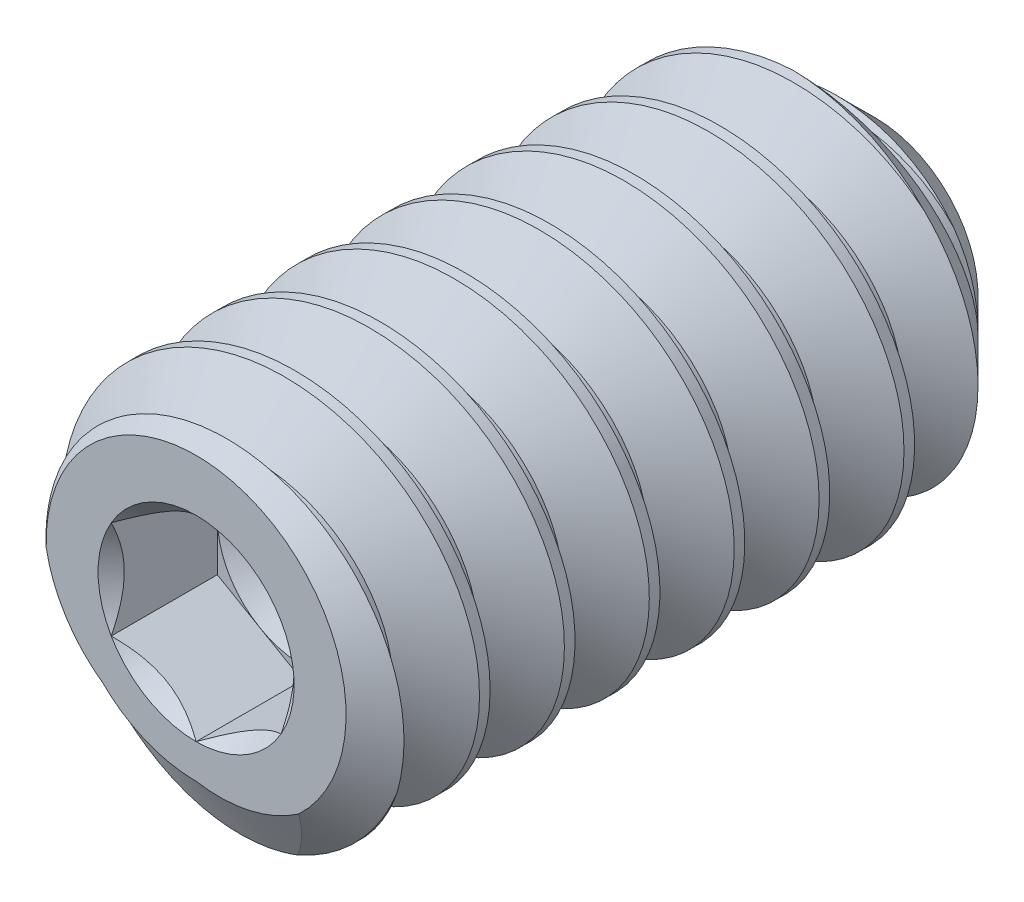
SolidWorks part; units mm, degrees
ref_plane "Front" through (0, 0, 0) normal (0, 0, 1) x (1, 0, 0)
ref_plane "Top" through (0, 0, 0) normal (0, 1, 0) x (1, 0, 0)
ref_plane "Right" through (0, 0, 0) normal (1, 0, 0) x (0, 0, -1)
sketch "Sketch22" plane through (0, 0, 0) normal (1, 0, 0) x (0, 0, -1)
  line L0 (-2.8865, 0) -> (-2.8865, 1.4021)
  line L1 (-2.8865, 1.4021) -> (-2.641, 1.7526)
  line L2 (-2.641, 1.7526) -> (2.6713, 1.7526)
  line L3 (2.6713, 1.7526) -> (3.4635, 0.9604)
  line L4 (3.4635, 0.9604) -> (2.8865, 0)
  line L5 (2.8865, 0) -> (-2.8865, 0)
  line L6 (2.8865, 0) -> (3.4635, 0) construction
  line L7 (3.4635, 0) -> (3.4635, 0.9604) construction
  line L8 (3.4635, -0.9604) -> (2.8865, 0) construction
  line L9 (-2.641, -1.7526) -> (2.6713, -1.7526) construction
  dimension "Dia" = 3.5052
  dimension "Length" = 6.35
  dimension "D3" = 35
  dimension "D5" = 118
  dimension "D6" = 45
  dimension "D7" = 2.8042
revolve "Revolve1" add sketch "Sketch22" angle 360 about L6
ref_plane "Plane1" through (0, 0, -3.4635) normal (0, 0, 1) x (1, 0, 0)
sketch "Sketch27" plane through (0, 0, -3.4635) normal (0, 0, 1) x (1, 0, 0)
  circle A0 centre (0, 0) radius 1.7526 construction
  circle A1 centre (0, 0) radius 1.7526
sketch "Sketch23" plane through (0, 0, 2.8865) normal (0, 0, 1) x (1, 0, 0)
  line L1 (0, 0.9165) -> (-0.7937, 0.4583)
  line L2 (-0.7937, 0.4583) -> (-0.7938, -0.4583)
  line L3 (-0.7938, -0.4583) -> (0, -0.9165)
  line L4 (0, -0.9165) -> (0.7937, -0.4583)
  line L5 (0.7937, -0.4583) -> (0.7937, 0.4583)
  line L6 (0.7937, 0.4583) -> (0, 0.9165)
  circle A0 centre (0, 0) radius 0.7938 construction
  dimension "Hex" = 1.5875
extrude "Cut-Extrude10" cut sketch "Sketch23" against normal blind 0.9922
sketch "Sketch24" plane through (0, 0, 2.8865) normal (0, 0, 1) x (1, 0, 0)
  circle A0 centre (0, 0) radius 0.9165
extrude "Cut-Extrude11" cut sketch "Sketch24" against normal through all draft 45
sketch "Sketch26" plane through (0, 0, 1.8943) normal (0, 0, 1) x (1, 0, 0)
  circle A0 centre (0, 0) radius 0.7938 construction
  circle A1 centre (0, 0) radius 0.7938
extrude "Cut-Extrude12" cut sketch "Sketch26" against normal through all draft 60
sketch "Sketch30" plane through (0, 0, 0) normal (1, 0, 0) x (0, 0, -1)
  line L0 (-2.641, 1.7526) -> (2.6713, 1.7526) construction
  line L1 (-2.8865, 0) -> (-2.8865, 1.4021) construction
  line L2 (3.4635, 0) -> (3.4635, 0.9604) construction
  line L3 (-2.641, -1.7526) -> (2.6713, -1.7526) construction
  point P0 (-2.8865, 1.7526)
  point P1 (3.4635, 1.7526)
  point P2 (3.4635, -1.7526)
  point P11 (0.6854, -1.7526)
  dimension "D1" = 2.7781
sketch "Sketch31" plane through (0, 0, 0) normal (1, 0, 0) x (0, 0, -1)
  line L2 (2.8865, 0) -> (3.4635, -0.9604)
  line L3 (3.4635, 0.9604) -> (2.8865, 0)
ref_axis "Center Axis 1" through (0, 0, -10.7974) along (0, 0, 1)
ref_plane "Contact Plane 1" through (0, 0, 2.8865) normal (0, 0, -1) x (0, 1, 0)
ref_plane "Contact Plane 2" through (0, 0, -3.4635) normal (0, 0, -1) x (0, 1, 0)
curve "Helix/Spiral1" pitch 0.7937 height 7.1437 radius 1.7526 centre (0, 0, -3.4635) axis (0, 0, 1) start towards (0, 1, 0)
sketch "Sketch28" plane through (0, 0, 0) normal (1, 0, 0) x (0, 0, -1)
  line L0 (3.4635, 1.7526) -> (4.1581, 1.7526)
  line L1 (4.1581, 1.7526) -> (3.8604, 1.237)
  line L2 (3.8604, 1.237) -> (3.7612, 1.237)
  line L3 (3.7612, 1.237) -> (3.4635, 1.7526)
  line L4 (3.6124, 1.4948) -> (4.0092, 1.4948) construction
  line L6 (-2.641, 1.7526) -> (2.6713, 1.7526) construction
  line L7 (3.4635, 1.0198) -> (3.4635, -1.0198) construction
  dimension "D1" = 0.0992
  dimension "D3" = 60
  dimension "D2" = 0.3969
sweep "Cut-Sweep2" cut profiles "Sketch28" path "Helix/Spiral1"
equation "\"D7@Sketch22\"=\"Dia@Sketch22\"*.8"
equation "\"D1@Sketch28\" = \"D4@Helix/Spiral1\" * .125"
equation "\"D3@Helix/Spiral1\" = \"Length@Sketch22\" + \"D4@Helix/Spiral1\""
equation "\"D1@Sketch30\" = \"D4@Helix/Spiral1\" * 3.5"
equation "\"hex Depth@Cut-Extrude10\" = \"Hex@Sketch23\" * .625"
equation "\"D2@Sketch28\" = \"D4@Helix/Spiral1\" * .5"
